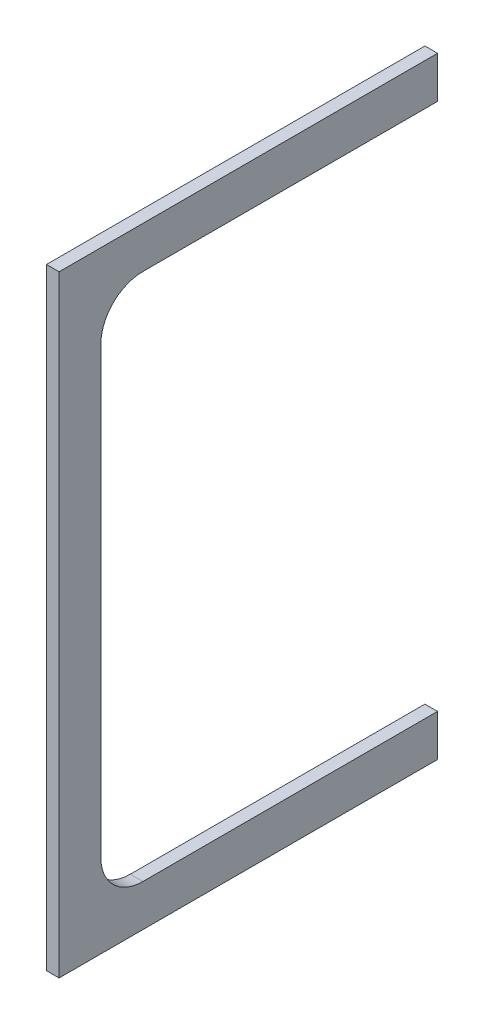
SolidWorks part; units mm, degrees
ref_plane "Спереди" through (0, 0, 0) normal (0, 0, 1) x (1, 0, 0)
ref_plane "Сверху" through (0, 0, 0) normal (0, 1, 0) x (1, 0, 0)
ref_plane "Справа" through (0, 0, 0) normal (1, 0, 0) x (0, 0, -1)
ref_plane "Плоскость4" through (-1.5, 0, 0) normal (-1, 0, 0) x (0, -1, 0)
sketch "Эскиз1" plane through (-1.5, 0, 0) normal (-1, 0, 0) x (0, -1, 0)
  line L0 (-138.5, -36.5) -> (-138.5, 33.5)
  line L1 (-128.5, 43.5) -> (-23, 43.5)
  line L2 (-13, 33.5) -> (-13, -36.5)
  line L3 (-13, -36.5) -> (-3.1, -36.5)
  line L4 (-3.1, -36.5) -> (-3.1, 53.4)
  line L5 (-3.1, 53.4) -> (-148.4, 53.4)
  line L6 (-148.4, 53.4) -> (-148.4, -36.5)
  line L7 (-148.4, -36.5) -> (-138.5, -36.5)
  arc A0 (-138.5, 33.5) -> (-128.5, 43.5) centre (-128.5, 33.5) cw
  arc A1 (-23, 43.5) -> (-13, 33.5) centre (-23, 33.5) cw
extrude "Бобышка-Вытянуть1" add sketch "Эскиз1" against normal blind 3
ref_axis "Ось1" through (0, 148.4, 53.4) along (0, -1, 0)
